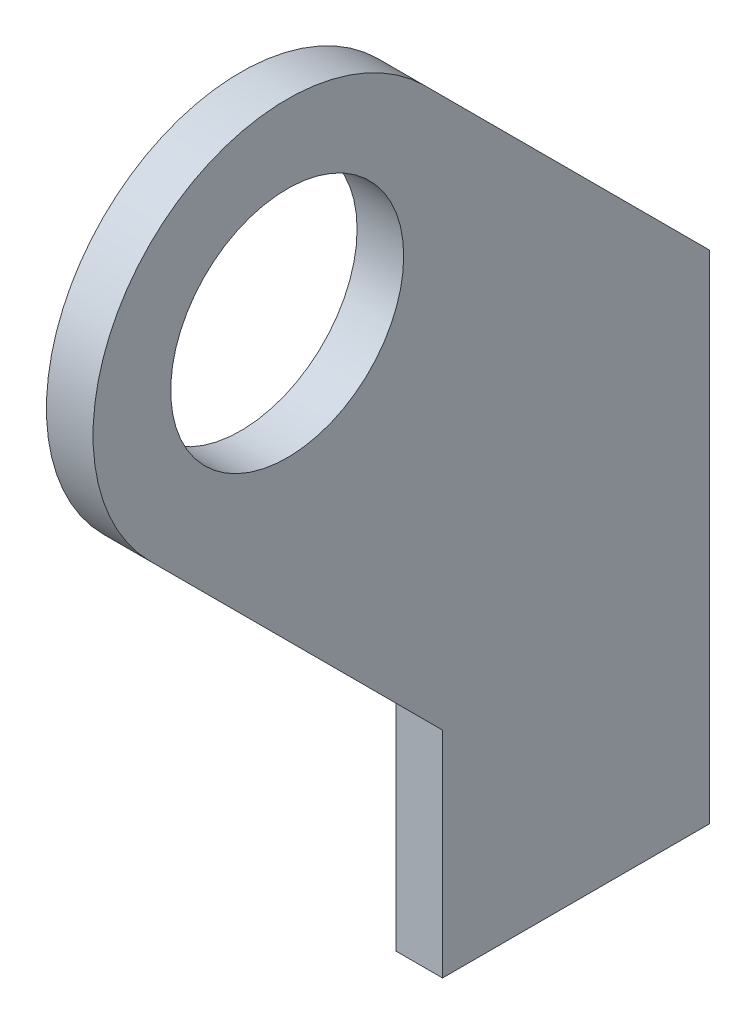
SolidWorks part; units mm, degrees
material "6061-T6 (SS)"
ref_plane "Front Plane" through (0, 0, 0) normal (0, 0, 1) x (1, 0, 0)
ref_plane "Top Plane" through (0, 0, 0) normal (0, 1, 0) x (1, 0, 0)
ref_plane "Right Plane" through (0, 0, 0) normal (1, 0, 0) x (0, 0, -1)
ref_axis "X" through (-88.99, 0, 0) along (1, 0, 0)
ref_axis "Y" through (0, 55, 0) along (0, -1, 0)
ref_axis "Z" through (0, 0, -88.99) along (0, 0, 1)
sketch "Sketch1" plane through (0, 0, 0) normal (1, 0, 0) x (0, 0, -1)
  line L0 (8.8388, 8.8388) -> (27.1777, -9.5)
  line L1 (27.1777, -9.5) -> (27.1777, -41.5)
  line L2 (27.1777, -41.5) -> (10, -41.5)
  line L3 (10, -41.5) -> (10, -27.6777)
  line L4 (10, -27.6777) -> (-8.8388, -8.8388)
  line L5 (10, -9.5) -> (10, -41.5) construction
  line L7 (10, -41.5) -> (70, -41.5) construction
  line L8 (10, -9.5) -> (70, -9.5) construction
  line L11 (8.8388, 8.8388) -> (25.6777, -8) construction
  circle A0 centre (0, 0) radius 7.5
  circle A1 centre (0, 0) radius 12.5
  dimension "D1" = 15
  dimension "D2" = 5
extrude "Boss-Extrude1" add sketch "Sketch1" along normal blind 3 contours A1 L4 L3 L2 L1 L0 | A1 A0 region at (0, -20.8632, -16.049) region at (0, 4.6482, -11.2219)
